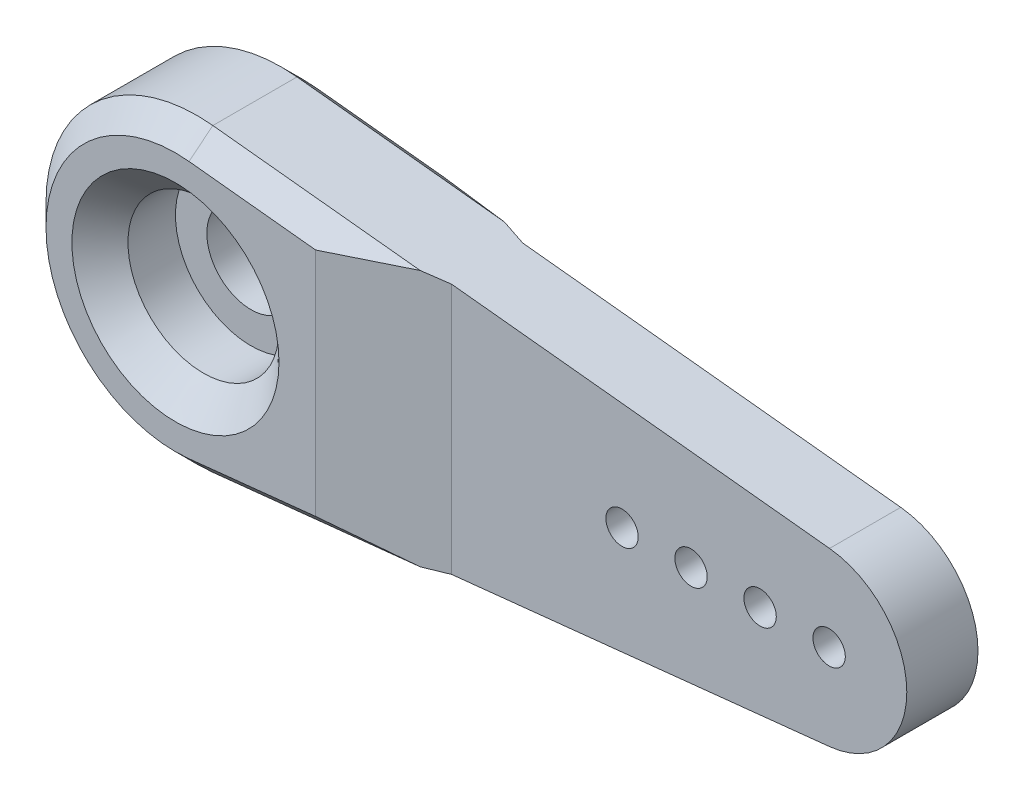
SolidWorks part; units mm, degrees
ref_plane "Plan de face" through (0, 0, 0) normal (0, 0, 1) x (1, 0, 0)
ref_plane "Plan de dessus" through (0, 0, 0) normal (0, 1, 0) x (1, 0, 0)
ref_plane "Plan de droite" through (0, 0, 0) normal (1, 0, 0) x (0, 0, -1)
sketch "Esquisse1" plane through (0, 0, 0) normal (0, 0, 1) x (1, 0, 0)
  line L0 (0, 0) -> (58.0381, 0) construction
  line L1 (0, 11.5762) -> (0, -10.9476) construction
  line L2 (28.6, 6.8619) -> (28.6, -5.6048) construction
  line L3 (0.7343, 6.9614) -> (29.0196, 3.9779) construction
  line L4 (29.0196, -3.9779) -> (0.7343, -6.9614) construction
  line L5 (0.7343, 6.9614) -> (29.0196, 3.9779)
  line L6 (29.0196, -3.9779) -> (0.7343, -6.9614)
  line L7 (-7, 0) -> (-7, 16.9861) construction
  line L8 (32.6, 0) -> (32.6, 13.2444) construction
  circle A0 centre (0, 0) radius 7 construction
  circle A1 centre (28.6, 0) radius 4 construction
  arc A2 (0.7343, 6.9614) -> (0.7343, -6.9614) centre (0, 0) ccw
  arc A3 (29.0196, 3.9779) -> (29.0196, -3.9779) centre (28.6, 0) cw
  circle A4 centre (0, 0) radius 2.0468
  dimension "D2" = 14
  dimension "D3" = 8
  dimension "D1" = 39.6
extrude "Boss.-Extru.1" add sketch "Esquisse1" along normal blind 3.3
sketch "Esquisse2" plane through (0, 0, 3.3) normal (0, 0, 1) x (1, 0, 0)
  line L0 (0.7343, -6.9614) -> (29.0196, -3.9779) construction
  line L1 (6.5, 11.5318) -> (6.5, -12.9458) construction
  line L2 (0.7343, 6.9614) -> (6.5, 6.3532)
  line L3 (29.0196, 3.9779) -> (0.7343, 6.9614) construction
  line L4 (6.5, 6.3532) -> (6.5, -6.3532)
  line L5 (6.5, -6.3532) -> (0.7343, -6.9614)
  arc A0 (0.7343, 6.9614) -> (0.7343, -6.9614) centre (0, 0) ccw
  circle A1 centre (0, 0) radius 2.0468
  dimension "D1" = 6.5
extrude "Boss.-Extru.2" add sketch "Esquisse2" along normal blind 1.3 and the other way offset from surface (4.6 mm away) 1.3 other way up to face at (13.8385, 0, 0)
chamfer "Chanfrein1" distance 5 distance2 1.3 1 edges at (6.5, 0, 3.3)
chamfer "Chanfrein3" distance 1.3 distance2 5 1 edges at (6.5, 0, 0)
chamfer "Chanfrein2" distance 1 angle 45 6 edges at (3.6171, 6.6573, 4.6) (3.6171, -6.6573, 4.6) (-7, 0, 4.6) (3.6171, -6.6573, -1.3) (3.6171, 6.6573, -1.3) (-7, 0, -1.3)
sketch "Esquisse3" plane through (0, 0, -1.3) normal (0, 0, -1) x (-1, 0, 0)
  circle A0 centre (0, 0) radius 5.5
  circle A1 centre (0, 0) radius 2.75
  dimension "D1" = 11
  dimension "D2" = 5.5
extrude "Boss.-Extru.3" add sketch "Esquisse3" along normal blind 1.8
chamfer "Chanfrein4" distance 1.5 angle 45 1 edges at (-5.5, 0, -3.1)
sketch "Esquisse4" plane through (0, 0, 4.6) normal (0, 0, 1) x (1, 0, 0)
  circle A0 centre (0, 0) radius 3.5
  dimension "D1" = 7
extrude "Enlèv. mat.-Extru.1" cut sketch "Esquisse4" against normal blind 3.5
chamfer "Chanfrein5" distance 1.3 angle 45 1 edges at (3.5, 0, 4.6)
sketch "Esquisse5" plane through (0, 0, 3.3) normal (0, 0, 1) x (1, 0, 0)
  line L0 (0, 0) -> (45.1885, 0) construction
  line L1 (29, 2.5592) -> (29, -2.5592) construction
  circle A0 centre (29, 0) radius 0.75
  circle A1 centre (25.8, 0) radius 0.75
  circle A2 centre (22.6, 0) radius 0.75
  circle A3 centre (19.4, 0) radius 0.75
  point P6 (29, 0)
  dimension "D2" = 1.5
  dimension "D1" = 29
  dimension "D3" = 4
extrude "Enlèv. mat.-Extru.2" cut sketch "Esquisse5" against normal blind 3.5
